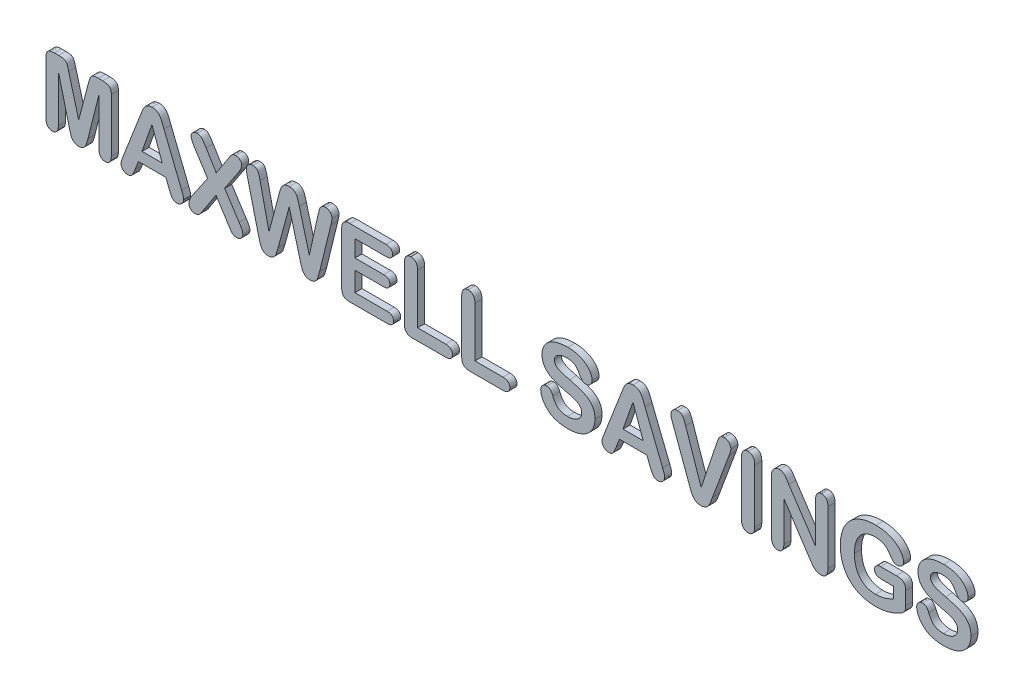
SolidWorks part; units mm, degrees
ref_plane "Front" through (0, 0, 0) normal (0, 0, 1) x (1, 0, 0)
ref_plane "Top" through (0, 0, 0) normal (0, 1, 0) x (1, 0, 0)
ref_plane "Right" through (0, 0, 0) normal (1, 0, 0) x (0, 0, -1)
sketch "Sketch1" plane through (0, 0, 0) normal (0, 0, 1) x (1, 0, 0)
  line L1 (-70.9822, -5) -> (70.9822, -5) construction
  line L2 (-70.9822, -5) -> (-70.9822, 5) construction
  line L3 (-70.9822, 5) -> (70.9822, 5) construction
  line L4 (70.9822, -5) -> (70.9822, 5) construction
  line L5 (-70.9822, -5) -> (70.9822, 5) construction
  line L6 (-70.9822, 5) -> (70.9822, -5) construction
  text T0 "MAXWELL SAVINGS"
  point P0 (0, 0)
  point P6 (50.3718, -5)
  point P8 (70.9822, -5)
  dimension "D1" = 10
extrude "Boss-Extrude1" add sketch "Sketch1" against normal blind 0.99 and the other way blind 0.01
